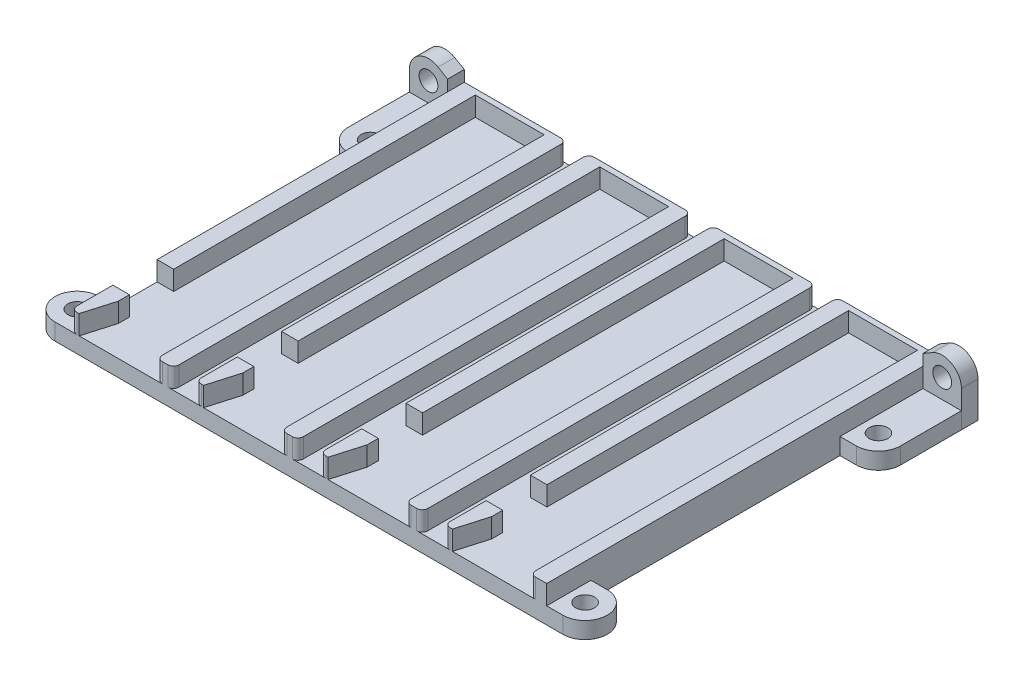
SolidWorks part; units mm, degrees
ref_plane "正面" through (0, 0, 0) normal (0, 0, 1) x (1, 0, 0)
ref_plane "平面" through (0, 0, 0) normal (0, 1, 0) x (1, 0, 0)
ref_plane "右側面" through (0, 0, 0) normal (1, 0, 0) x (0, 0, -1)
sketch "ｽｹｯﾁ2" plane through (0, 0, 0) normal (0, 1, 0) x (1, 0, 0)
  line L1 (0, 0) -> (85.95, 0)
  line L2 (0, 8) -> (0, 53.05)
  line L3 (0, 71.05) -> (85.95, 71.05)
  line L6 (85.95, 71.05) -> (85.95, 68.05)
  line L7 (85.95, 0) -> (88.895, 0)
  line L8 (85.95, 8) -> (88.895, 8)
  line L9 (88.895, 8) -> (88.895, 0) construction
  line L12 (0, 71.05) -> (0, 68.05)
  line L13 (0, 0) -> (-2.945, 0)
  line L14 (0, 8) -> (-2.945, 8)
  line L15 (-2.945, 8) -> (-2.945, 0) construction
  line L17 (88.895, 53.05) -> (85.95, 53.05)
  line L18 (85.95, 53.05) -> (85.95, 8)
  line L20 (-2.945, 53.05) -> (0, 53.05)
  line L21 (-6.945, 57.05) -> (-6.945, 68.05)
  line L22 (-6.945, 68.05) -> (0, 68.05)
  line L23 (92.895, 57.05) -> (92.895, 68.05)
  line L24 (92.895, 68.05) -> (85.95, 68.05)
  arc A2 (88.895, 0) -> (88.895, 8) centre (88.895, 4) ccw
  circle A3 centre (88.895, 4) radius 1.7
  arc A6 (-2.945, 8) -> (-2.945, 0) centre (-2.945, 4) ccw
  circle A7 centre (-2.945, 4) radius 1.7
  arc A8 (92.895, 57.05) -> (88.895, 53.05) centre (88.895, 57.05) cw
  circle A9 centre (88.895, 57.05) radius 1.7
  arc A10 (-6.945, 57.05) -> (-2.945, 53.05) centre (-2.945, 57.05) ccw
  circle A11 centre (-2.945, 57.05) radius 1.7
  dimension "D3" = 2.945
  dimension "D4" = 4
  dimension "D6" = 3.4
  dimension "D1" = 71.05
  dimension "D2" = 85.95
  dimension "D5" = 3
  dimension "D7" = 15
extrude "ﾎﾞｽ - 押し出し1" add sketch "ｽｹｯﾁ2" along normal blind 3
sketch "ｽｹｯﾁ3" plane through (0, 3, 0) normal (0, 1, 0) x (1, 0, 0)
  line L8 (-2.945, 0) -> (88.895, 0) construction
  line L15 (68.9, 0) -> (70.5, 5.5)
  line L16 (70.5, 5.5) -> (70.5, 7.5)
  line L17 (70.5, 7.5) -> (67.5, 7.5)
  line L18 (67.5, 7.5) -> (67.5, 0)
  line L19 (67.5, 0) -> (68.9, 0)
  line L20 (67.5, 15.5) -> (70.5, 15.5)
  line L21 (70.5, 15.5) -> (70.5, 70.05)
  line L22 (70.5, 70.05) -> (82.95, 70.05)
  line L23 (82.95, 70.05) -> (82.95, 0)
  line L24 (82.95, 0) -> (85.95, 0)
  line L26 (85.95, 71.05) -> (67.5, 71.05)
  line L27 (67.5, 71.05) -> (67.5, 15.5)
  line L28 (76.725, 70.05) -> (76.725, 0) construction
  line L67 (45, 15.5) -> (48, 15.5)
  line L68 (48, 15.5) -> (48, 70.05)
  line L69 (48, 70.05) -> (60.45, 70.05)
  line L70 (60.45, 70.05) -> (60.45, 0)
  line L71 (60.45, 0) -> (63.45, 0)
  line L72 (63.45, 0) -> (63.45, 71.05)
  line L73 (63.45, 71.05) -> (45, 71.05)
  line L74 (45, 71.05) -> (45, 15.5)
  line L75 (46.4, 0) -> (48, 5.5)
  line L76 (48, 5.5) -> (48, 7.5)
  line L77 (48, 7.5) -> (45, 7.5)
  line L78 (45, 7.5) -> (45, 0)
  line L79 (45, 0) -> (46.4, 0)
  line L80 (22.5, 15.5) -> (25.5, 15.5)
  line L81 (25.5, 15.5) -> (25.5, 70.05)
  line L82 (25.5, 70.05) -> (37.95, 70.05)
  line L83 (37.95, 70.05) -> (37.95, 0)
  line L84 (37.95, 0) -> (40.95, 0)
  line L85 (40.95, 0) -> (40.95, 71.05)
  line L86 (40.95, 71.05) -> (22.5, 71.05)
  line L87 (22.5, 71.05) -> (22.5, 15.5)
  line L88 (23.9, 0) -> (25.5, 5.5)
  line L89 (25.5, 5.5) -> (25.5, 7.5)
  line L90 (25.5, 7.5) -> (22.5, 7.5)
  line L91 (22.5, 7.5) -> (22.5, 0)
  line L92 (22.5, 0) -> (23.9, 0)
  line L93 (0, 15.5) -> (3, 15.5)
  line L94 (3, 15.5) -> (3, 70.05)
  line L95 (3, 70.05) -> (15.45, 70.05)
  line L96 (15.45, 70.05) -> (15.45, 0)
  line L97 (15.45, 0) -> (18.45, 0)
  line L98 (18.45, 0) -> (18.45, 71.05)
  line L99 (18.45, 71.05) -> (0, 71.05)
  line L100 (0, 71.05) -> (0, 15.5)
  line L101 (1.4, 0) -> (3, 5.5)
  line L102 (3, 5.5) -> (3, 7.5)
  line L103 (3, 7.5) -> (0, 7.5)
  line L104 (0, 7.5) -> (0, 0)
  line L105 (0, 0) -> (1.4, 0)
  line L107 (85.95, 71.05) -> (85.95, 0)
  dimension "D1" = 12.45
  dimension "D2" = 1
  dimension "D3" = 7.5
  dimension "D4" = 2
  dimension "D5" = 8
  dimension "D6" = 1.6
  dimension "D7" = 3
  dimension "D8" = 4
  dimension "D9" = 4.05
extrude "ﾎﾞｽ - 押し出し2" add sketch "ｽｹｯﾁ3" along normal blind 3.5
fillet "ﾌｨﾚｯﾄ7" radius 1 17 edges at (67.5, 4.75, 0) (67.5, 4.75, -71.05) (63.45, 4.75, -71.05) (45, 4.75, -71.05) (40.95, 4.75, -71.05) (22.5, 4.75, -71.05) (18.45, 4.75, -71.05) (63.45, 4.75, 0) (60.45, 4.75, 0) (45, 4.75, 0) (40.95, 4.75, 0) (37.95, 4.75, 0) (22.5, 4.75, 0) (18.45, 4.75, 0) (15.45, 4.75, 0) (82.95, 4.75, 0) (0, 4.75, 0)
sketch "ｽｹｯﾁ6" plane through (0, 0, -71.05) normal (0, 0, -1) x (-1, 0, 0)
  line L0 (-85.95, 0) -> (-92.9, 0)
  line L1 (-92.9, 0) -> (-92.9, 6.5)
  line L2 (-85.95, 6.5) -> (-85.95, 0)
  line L3 (0, 0) -> (0, 6.5)
  line L4 (6.95, 6.5) -> (6.95, 0)
  line L5 (6.95, 0) -> (0, 0)
  line L6 (-17.45, 6.5) -> (0, 6.5) construction
  line L7 (-85.95, 6.5) -> (-85.95, 8.5)
  line L8 (0, 6.5) -> (0, 8.5)
  line L9 (-85.95, 8.5) -> (-87.6793, 9.5047)
  line L10 (0, 8.5) -> (1.7293, 9.5047)
  line L11 (-85.95, 6.5) -> (-68.5, 6.5) construction
  arc A0 (-92.9, 6.5) -> (-87.6793, 9.5047) centre (-89.425, 6.5) cw
  arc A1 (1.7293, 9.5047) -> (6.95, 6.5) centre (3.475, 6.5) cw
  circle A2 centre (-89.425, 6.5) radius 1.7
  circle A3 centre (3.475, 6.5) radius 1.7
  dimension "D2" = 3.4
  dimension "D1" = 6.95
  dimension "D3" = 2
extrude "ﾎﾞｽ - 押し出し3" add sketch "ｽｹｯﾁ6" against normal blind 3
